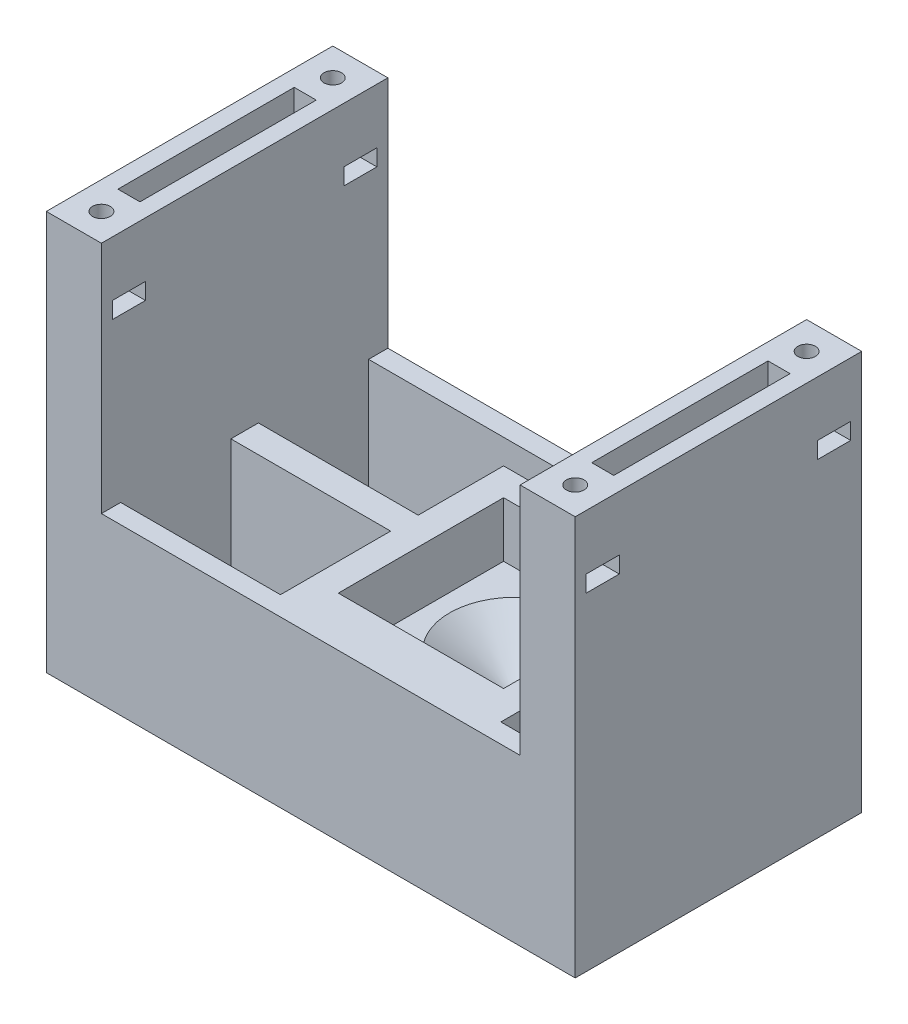
SolidWorks part; units mm, degrees
material "ABS"
ref_plane "Front Plane" through (0, 0, 0) normal (0, 0, 1) x (1, 0, 0)
ref_plane "Top Plane" through (0, 0, 0) normal (0, 1, 0) x (1, 0, 0)
ref_plane "Right Plane" through (0, 0, 0) normal (1, 0, 0) x (0, 0, -1)
other "Center of Mass"
sketch "Sketch1" plane through (0, 0, 0) normal (0, 1, 0) x (1, 0, 0)
  line L0 (0, -55) -> (0, 55) construction
  line L1 (-61, 26) -> (35, 26)
  line L2 (-61, 26) -> (-61, -26)
  line L3 (-61, -26) -> (35, -26)
  line L4 (35, 26) -> (35, -26)
  line L5 (-55, 0) -> (55, 0) construction
  dimension "D1" = 96
  dimension "D2" = 52
  dimension "D3" = 35
  dimension "D4" = 26
extrude "Boss-Extrude1" add sketch "Sketch1" along normal blind 30
sketch "Sketch3" plane through (0, 30, 0) normal (0, 1, 0) x (1, 0, 0)
  line L0 (35, -26) -> (35, 26) construction
  line L1 (-17, 13) -> (13, 13)
  line L2 (-17, 13) -> (-17, -17)
  line L3 (-17, -17) -> (13, -17)
  line L4 (13, 13) -> (13, -17)
  line L7 (35, 26) -> (-61, 26) construction
  dimension "D1" = 22
  dimension "D2" = 30
  dimension "D3" = 13
  dimension "D4" = 30
extrude "Cut-Extrude1" cut sketch "Sketch3" against normal blind 10
sketch "Sketch4" plane through (0, 30, 0) normal (0, 1, 0) x (1, 0, 0)
  line L0 (-61, -26) -> (35, -26) construction
  line L1 (35, 26) -> (25, 26)
  line L2 (35, 26) -> (35, -26)
  line L3 (35, -26) -> (25, -26)
  line L4 (25, 26) -> (25, -26)
  line L7 (-61, 26) -> (-51, 26)
  line L8 (-61, 26) -> (-61, -26)
  line L9 (-61, -26) -> (-51, -26)
  line L10 (-51, 26) -> (-51, -26)
  dimension "D1" = 10
  dimension "D2" = 10
extrude "Boss-Extrude2" add sketch "Sketch4" along normal blind 42.5
sketch "Sketch5" plane through (0, 30, 0) normal (0, 1, 0) x (1, 0, 0)
  line L0 (-51, -26) -> (25, -26) construction
  line L1 (-51, 22.5) -> (25, 22.5)
  line L2 (-51, 22.5) -> (-51, 2.5)
  line L3 (-51, -22.5) -> (-22, -22.5)
  line L4 (25, 22.5) -> (25, 2.5)
  line L5 (-22, 18) -> (18, 18)
  line L6 (-22, 18) -> (-22, 2.5)
  line L8 (18, 18) -> (18, 2.5)
  line L9 (25, 26) -> (25, -26) construction
  line L10 (-61, 26) -> (-61, -26) construction
  line L11 (-2, -17) -> (-2, 30.9744) construction
  line L12 (18, 2.5) -> (25, 2.5)
  line L13 (25, -2.5) -> (25, -22.5)
  line L14 (18, -2.5) -> (25, -2.5)
  line L16 (-4.5, 22.5) -> (0.5, 22.5)
  line L17 (-4.5, 22.5) -> (-4.5, 18)
  line L18 (-4.5, 18) -> (0.5, 18)
  line L19 (0.5, 22.5) -> (0.5, 18)
  line L20 (-22, 2.5) -> (-51, 2.5)
  line L21 (18, -2.5) -> (18, -20)
  line L22 (-22, -2.5) -> (-51, -2.5)
  line L23 (18, -22.5) -> (25, -22.5)
  line L24 (-17, -17) -> (13, -17) construction
  line L27 (13, 13) -> (-17, 13) construction
  line L28 (-17, 13) -> (-17, -17) construction
  line L29 (13, -17) -> (13, 13) construction
  line L31 (-55, 0) -> (55, 0) construction
  line L32 (-51, -2.5) -> (-51, -22.5)
  line L33 (-22, -2.5) -> (-22, -20)
  line L35 (-22, -20) -> (-22, -22.5)
  line L36 (18, -20) -> (18, -22.5)
  dimension "D1" = 10
  dimension "D2" = 45
  dimension "D3" = 3.5
  dimension "D4" = 0
  dimension "D5" = 2.5
  dimension "D6" = 2.5
  dimension "D7" = 5
  dimension "D8" = 5
  dimension "D9" = 5
  dimension "D11" = 2.5
  dimension "D12" = 2.5
  dimension "D13" = 2.5
  dimension "D14" = 2.5
extrude "Cut-Extrude2" cut sketch "Sketch5" against normal blind 25 contours L1 L19 L5 L8 L12 L4 | L20 L6 L5 L17 L1 L2 | L33 L22 L32 L3 | L23 L13 L14 L21 region at (-33.7206, 30, -13.4265) region at (12.75, 30, -22.1837) region at (-36.5, 30, 12.5) region at (21.5, 30, 12.5)
sketch "Sketch6" plane through (0, 0, 0) normal (0, -1, 0) x (1, 0, 0)
  line L0 (-2, 31.388) -> (-2, -34.0346) construction
  line L1 (35, 26) -> (35, -26) construction
  line L2 (55, 0) -> (-55, 0) construction
  circle A0 centre (-2, 0) radius 1.8
  dimension "D2" = 3.6
  dimension "D1" = 37
extrude "Cut-Extrude3" cut sketch "Sketch6" against normal through all
sketch "Sketch7" plane through (0, 0, 0) normal (0, -1, 0) x (1, 0, 0)
  circle A0 centre (-2, 0) radius 4
  circle A1 centre (-2, 0) radius 10
  dimension "D1" = 8
  dimension "D2" = 20
extrude "Cut-Extrude4" cut sketch "Sketch7" against normal blind 10
fillet "Fillet2" radius 2 1 edges at (-2, 10, -4)
fillet "Fillet3" radius 4 1 edges at (-2, 10, -10)
chamfer "Chamfer1" distance 10 angle 35 1 edges at (-2, 20, 1.8) first distance on face at (-2, 20, 1.8)
sketch "Sketch10" plane through (35, 0, 0) normal (1, 0, 0) x (0, 0, -1)
  line L1 (26, 72.5) -> (26, 0) construction
  line L2 (18, 59.5) -> (24, 59.5)
  line L3 (18, 59.5) -> (18, 62.5)
  line L4 (18, 62.5) -> (24, 62.5)
  line L5 (24, 59.5) -> (24, 62.5)
  line L6 (18, 59.5) -> (24, 62.5) construction
  line L7 (18, 62.5) -> (24, 59.5) construction
  line L8 (-26, 72.5) -> (26, 72.5) construction
  line L9 (0, 79.5181) -> (0, 55.2752) construction
  line L10 (0, 55) -> (0, -55) construction
  line L11 (-18, 59.5) -> (-24, 59.5)
  line L12 (-24, 59.5) -> (-24, 62.5)
  line L13 (-18, 62.5) -> (-24, 62.5)
  line L14 (-18, 59.5) -> (-18, 62.5)
  point P0 (21, 61)
  dimension "D1" = 5
  dimension "D2" = 6
  dimension "D3" = 3
  dimension "D4" = 10
extrude "Cut-Extrude7" cut sketch "Sketch10" against normal through all
sketch "Sketch11" plane through (0, 72.5, 0) normal (0, 1, 0) x (1, 0, 0)
  line L0 (-61, 26) -> (35, 26) construction
  line L1 (-58, 16) -> (-54, 16)
  line L2 (-58, 16) -> (-58, -16)
  line L3 (-58, -16) -> (-54, -16)
  line L4 (-54, 16) -> (-54, -16)
  line L5 (-13, 26) -> (-13, -31.3769) construction
  line L6 (-61, 26) -> (-61, -26) construction
  line L7 (-51, -26) -> (-51, 26) construction
  line L8 (-61, -26) -> (-51, -26) construction
  line L9 (32, -16) -> (28, -16)
  line L10 (28, 16) -> (28, -16)
  line L11 (32, 16) -> (32, -16)
  line L12 (32, 16) -> (28, 16)
  circle A0 centre (-56, 21) radius 1.6
  circle A1 centre (-56, -21) radius 1.6
  circle A2 centre (30, -21) radius 1.6
  circle A3 centre (30, 21) radius 1.6
  point P20 (-56, -26)
  dimension "D3" = 3.2
  dimension "D10" = 3.2
  dimension "D1" = 5
  dimension "D2" = 5
  dimension "D4" = 10
  dimension "D5" = 3
  dimension "D6" = 3
  dimension "D7" = 10
  dimension "D8" = 5
  dimension "D9" = 5
extrude "Cut-Extrude8" cut sketch "Sketch11" against normal blind 60
